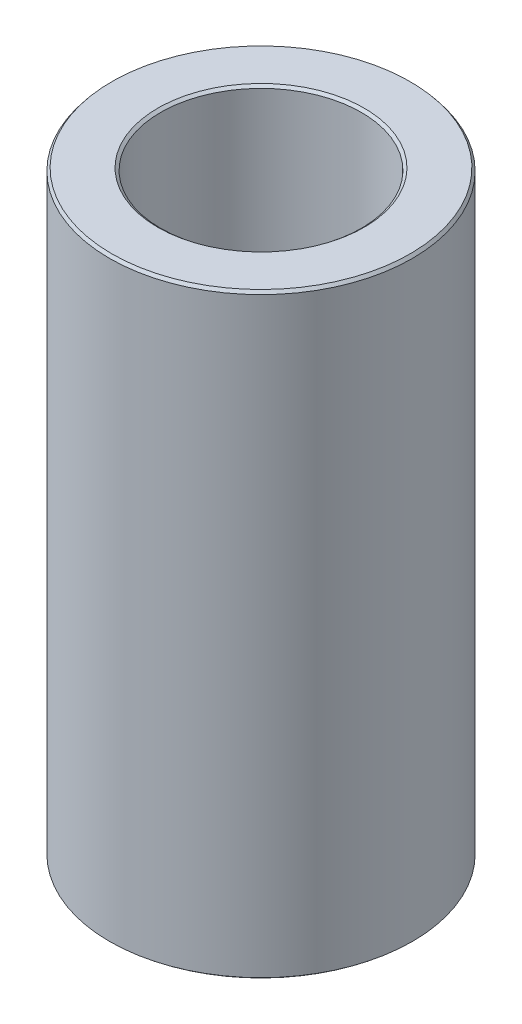
SolidWorks part; units mm, degrees
ref_plane "Front Plane" through (0, 0, 0) normal (0, 0, 1) x (1, 0, 0)
ref_plane "Top Plane" through (0, 0, 0) normal (0, 1, 0) x (1, 0, 0)
ref_plane "Right Plane" through (0, 0, 0) normal (1, 0, 0) x (0, 0, -1)
sketch "Sketch1" plane through (0, 0, 0) normal (0, 1, 0) x (1, 0, 0)
  circle A0 centre (0, 0) radius 45
  dimension "SLEEVE_OD" = 90
extrude "Boss-Extrude1" add sketch "Sketch1" along normal blind 177.3165
sketch "Sketch2" plane through (0, 0, 0) normal (0, 1, 0) x (1, 0, 0)
  circle A0 centre (0, 0) radius 29.8356
  dimension "BORE_D" = 59.6711
extrude "Cut-Extrude1" cut sketch "Sketch2" along normal through all
chamfer "Chamfer1" distance 0.8457 angle 38.519 4 edges at (0, 177.3165, 29.8356) (0, 0, 29.8356) (0, 0, 45) (0, 177.3165, 45) first distance on face at (0, 177.3165, 29.8356) first distance on face at (0, 0, 29.8356) first distance on face at (0, 177.3165, 45)
